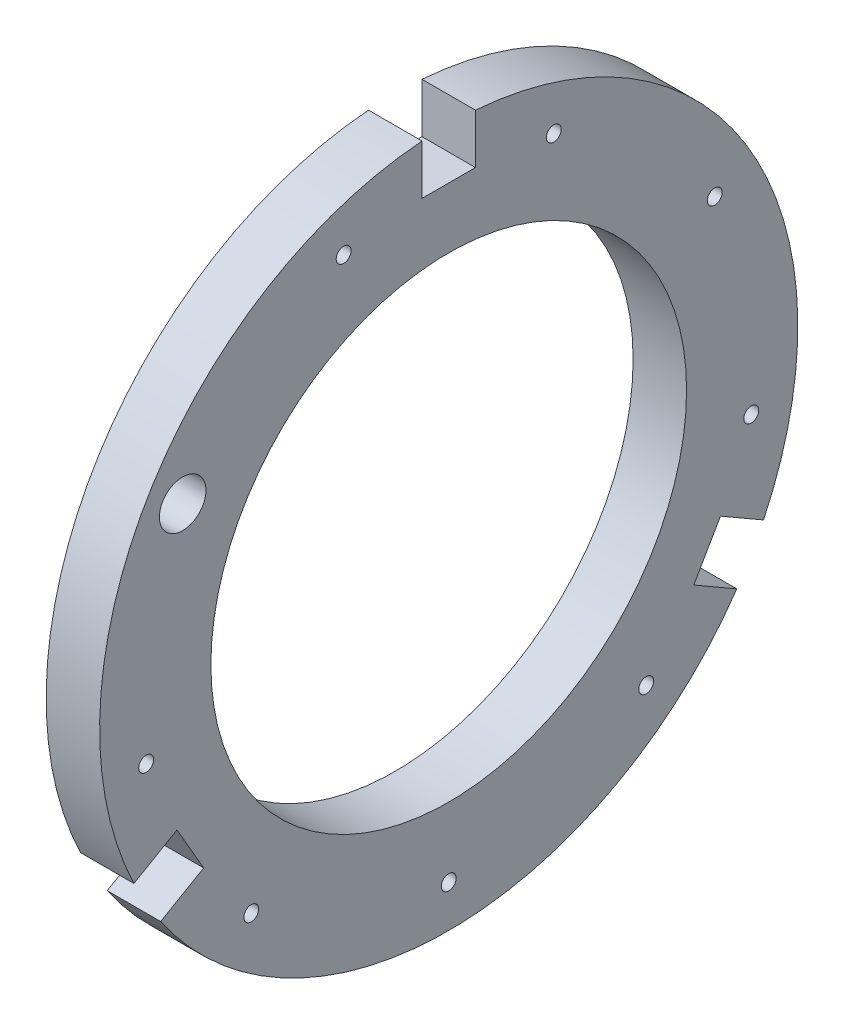
SolidWorks part; units mm, degrees
material "Teck"
ref_plane "Plan de face" through (0, 0, 0) normal (0, 0, 1) x (1, 0, 0)
ref_plane "Plan de dessus" through (0, 0, 0) normal (0, 1, 0) x (1, 0, 0)
ref_plane "Plan de droite" through (0, 0, 0) normal (1, 0, 0) x (0, 0, -1)
sketch "Esquisse1" plane through (0, 0, 0) normal (1, 0, 0) x (0, 0, -1)
  line L0 (0, 0) -> (0, 51.1) construction
  line L1 (0, 51.1) -> (-5.741, 51.1) construction
  line L2 (-5.741, 51.1) -> (-5.741, 64.1) construction
  line L3 (-5.741, 64.1) -> (-5.741, 74.7799)
  line L4 (-5.741, 64.1) -> (5.741, 64.1)
  line L5 (5.741, 64.1) -> (5.741, 74.7799)
  line L6 (58.3827, -27.0781) -> (67.6318, -32.4181)
  line L7 (58.3827, -27.0781) -> (52.6417, -37.0219)
  line L8 (52.6417, -37.0219) -> (61.8908, -42.3618)
  line L9 (-52.6417, -37.0219) -> (-61.8908, -42.3618)
  line L10 (-52.6417, -37.0219) -> (-58.3827, -27.0781)
  line L11 (-58.3827, -27.0781) -> (-67.6318, -32.4181)
  circle A0 centre (0, 0) radius 51.1
  circle A1 centre (0, 0) radius 75 construction
  arc A2 (-5.741, 74.7799) -> (-67.6318, -32.4181) centre (0, 0) ccw
  arc A3 (-61.8908, -42.3618) -> (61.8908, -42.3618) centre (0, 0) ccw
  arc A4 (67.6318, -32.4181) -> (5.741, 74.7799) centre (0, 0) ccw
  point P20 (0, 0)
  dimension "D1" = 102.2
  dimension "D2" = 150
  dimension "D3" = 5.741
  dimension "D4" = 13
  dimension "D5" = 11.482
  dimension "D6" = 3
extrude "Boss.-Extru.1" add sketch "Esquisse1" along normal blind 11.482
sketch "Sketch1" plane through (0, 0, 0) normal (1, 0, 0) x (0, 0, -1)
  line L0 (0, 0) -> (0, 40) construction
  line L1 (0, 0) -> (22.5733, 62.0197) construction
  circle A0 centre (22.5733, 62.0197) radius 1.6
  circle A1 centre (57.1577, 33) radius 1.6
  circle A2 centre (64.9973, -11.4608) radius 1.6
  circle A3 centre (42.424, -50.5589) radius 1.6
  circle A4 centre (0, -66) radius 1.6
  circle A5 centre (-42.424, -50.5589) radius 1.6
  circle A6 centre (-64.9973, -11.4608) radius 1.6
  circle A7 centre (-57.1577, 33) radius 1.6
  circle A8 centre (-22.5733, 62.0197) radius 1.6
  point P23 (0, 0)
  dimension "D4" = 3.2
  dimension "D1" = 40
  dimension "D2" = 66
  dimension "D3" = 20
  dimension "D5" = 9
extrude "Cut-Extrude1" cut sketch "Sketch1" against normal through all and the other way through all
sketch "Esquisse4" plane through (0, 0, 0) normal (1, 0, 0) x (0, 0, -1)
  line L0 (0, 0) -> (-57.1577, 33) construction
  line L1 (0, 0) -> (0, 41.2211) construction
  line L2 (-57.1577, 33) -> (-54.6577, 37.3301) construction
  line L3 (-57.1577, 33) -> (-59.6577, 28.6699) construction
  circle A0 centre (-57.1577, 33) radius 5
  dimension "D1" = 10
  dimension "D2" = 66
  dimension "D3" = 60
extrude "Enlèv. mat.-Extru.3" cut sketch "Esquisse4" against normal through all and the other way through all
equation "\"d_i_tube\"= 150mm'Inner Rocket Body Composite Tube Diameter"
equation "\"t_tube\"= 1.182mm'Thickness of Rocket Body Composite Tube"
equation "\"l_upper_body_tube\"= 1190mm'Upper Rocket Body Composite Tube length"
equation "\"l_lower_body_tube\"= 896mm'Lower Rocket Body Composite Tube Length"
equation "\"d_a_NC\"= 154mm'Outer Diameter of Nosecone base"
equation "\"d_i_phenolic_tube\"= 152.3mm'Inner Phenolic Tube Diameter"
equation "\"t_phenolic_tube\"= 2mm'Thickness of Phenolic Body Tube"
equation "\"l_fin_cut\"= 220mm'Length of fin on Motor Retainer"
equation "\"t_SW-Panel\"= 11.482mm'Thickness of Sandwich-Panel"
equation "\"l_motor_tube\"=650mm'Length of phenolic motor tube"
equation "\"d_i_motor_tube\"=99.06mm'Inner diameter of phenolic motor tube"
equation "\"t_motor_tube\"=1.58mm'Thicknes of phenolic motor tube"
equation "\"D2@Esquisse1\"=\"d_i_tube\""
equation "\"l_cut_fin_centering\"=13mm'Length of cut for fin alignement on fin centering rings"
equation "\"D3@Esquisse1\"= \"t_SW-Panel\" / 2"
equation "\"D4@Esquisse1\"=\"l_cut_fin_centering\""
equation "\"D5@Esquisse1\"=\"t_SW-Panel\""
equation "\"D1@Boss.-Extru.1\"=\"t_SW-Panel\""
